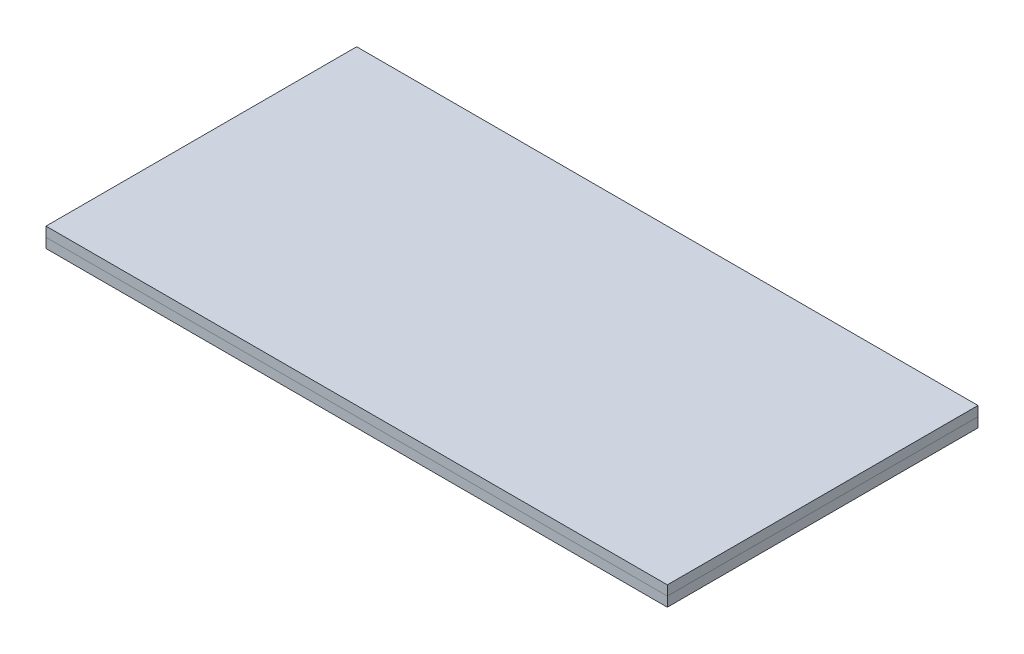
SolidWorks part; units mm, degrees
ref_plane "Front Plane" through (0, 0, 0) normal (0, 0, 1) x (1, 0, 0)
ref_plane "Top Plane" through (0, 0, 0) normal (0, 1, 0) x (1, 0, 0)
ref_plane "Right Plane" through (0, 0, 0) normal (1, 0, 0) x (0, 0, -1)
sketch "Sketch1" plane through (0, 0, 0) normal (0, 1, 0) x (1, 0, 0)
  line L1 (-609.6, -304.8) -> (609.6, -304.8)
  line L2 (-609.6, -304.8) -> (-609.6, 304.8)
  line L3 (-609.6, 304.8) -> (609.6, 304.8)
  line L4 (609.6, -304.8) -> (609.6, 304.8)
  line L5 (-609.6, -304.8) -> (609.6, 304.8) construction
  line L6 (-609.6, 304.8) -> (609.6, -304.8) construction
  point P0 (0, 0)
  dimension "D1" = 1219.2
  dimension "D2" = 609.6
extrude "MDF_Slab1" add sketch "Sketch1" along normal blind 19.05
sketch "Sketch2" plane through (0, 19.05, 0) normal (0, 1, 0) x (1, 0, 0)
  line L1 (609.6, -304.8) -> (-609.6, -304.8)
  line L2 (609.6, -304.8) -> (609.6, 304.8)
  line L3 (609.6, 304.8) -> (-609.6, 304.8)
  line L4 (-609.6, -304.8) -> (-609.6, 304.8)
  line L5 (609.6, -304.8) -> (-609.6, 304.8) construction
  line L6 (609.6, 304.8) -> (-609.6, -304.8) construction
  point P0 (0, 0)
extrude "MDF_Slab2" add sketch "Sketch2" along normal blind 19.05 separate body
